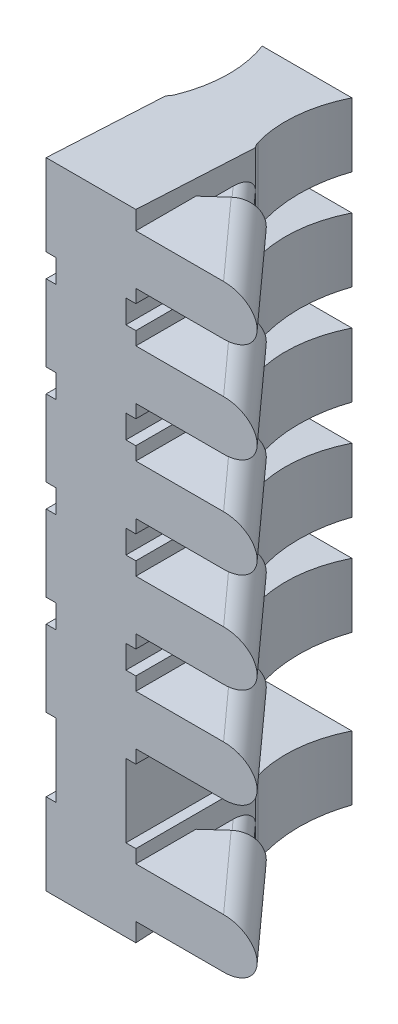
SolidWorks part; units mm, degrees
ref_plane "Front Plane" through (0, 0, 0) normal (0, 0, 1) x (1, 0, 0)
ref_plane "Top Plane" through (0, 0, 0) normal (0, 1, 0) x (1, 0, 0)
ref_plane "Right Plane" through (0, 0, 0) normal (1, 0, 0) x (0, 0, -1)
sketch "Sketch1" plane through (0, 0, 0) normal (0, 0, 1) x (1, 0, 0)
  line L0 (-7.5, 0) -> (0, 0) construction
  line L1 (-7.5, 15) -> (7.5, 15)
  line L2 (-7.5, 15) -> (-7.5, -15)
  line L3 (-7.5, -15) -> (7.5, -15)
  line L4 (7.5, 15) -> (7.5, -15)
  line L5 (0, 0) -> (0, 15) construction
  dimension "D1" = 15
  dimension "D2" = 30
sketch "Sketch2" plane through (0, 0, 0) normal (1, 0, 0) x (0, 0, -1)
  line L1 (0, 15) -> (7, 15)
  line L2 (0, 15) -> (0, -15)
  line L3 (0, -15) -> (7, -15)
  line L4 (7, 15) -> (7, -15)
  dimension "D1" = 7
extrude "Boss-Extrude1" add sketch "Sketch1" against normal up to vertex (7 mm away) up to point (0, 15, -7)
ref_plane "Plane1" through (1.35, 0, 0) normal (1, 0, 0) x (0, 0, -1)
sketch "Sketch7" plane through (1.35, 0, 0) normal (1, 0, 0) x (0, 0, -1)
  line L0 (3, 4.1005) -> (0, 4.1005) construction
  line L1 (0, 4.1005) -> (0, 6.3995) construction
  line L2 (3, 6.3995) -> (0, 6.3995) construction
  line L3 (3, 6.3995) -> (6.5, 6.2161) construction
  line L4 (6.5, 6.2161) -> (6.5, 4.2839) construction
  line L5 (6.5, 4.2839) -> (3, 4.1005) construction
  line L6 (3, 1.1005) -> (0, 1.1005) construction
  line L7 (0, 1.1005) -> (0, 3.3995) construction
  line L8 (3, 3.3995) -> (0, 3.3995) construction
  line L9 (6.5, 3.2161) -> (3, 3.3995) construction
  line L10 (6.5, 1.2839) -> (6.5, 3.2161) construction
  line L11 (3, 1.1005) -> (6.5, 1.2839) construction
  line L12 (3, -1.8995) -> (0, -1.8995) construction
  line L13 (0, -1.8995) -> (0, 0.3995) construction
  line L14 (3, 0.3995) -> (0, 0.3995) construction
  line L15 (3, 0.3995) -> (6.5, 0.2161) construction
  line L16 (6.5, 0.2161) -> (6.5, -1.7161) construction
  line L17 (6.5, -1.7161) -> (3, -1.8995) construction
  line L19 (3, -4.8995) -> (0, -4.8995) construction
  line L20 (0, -4.8995) -> (0, -2.6005) construction
  line L21 (3, -2.6005) -> (0, -2.6005) construction
  line L22 (6.5, -2.7839) -> (3, -2.6005) construction
  line L23 (6.5, -4.7161) -> (6.5, -2.7839) construction
  line L24 (3, -4.8995) -> (6.5, -4.7161) construction
  line L25 (3, -7.1005) -> (0, -7.1005) construction
  line L26 (0, -9.5567) -> (0, -7.1005) construction
  line L27 (6.5, -9.2161) -> (0, -9.5567) construction
  line L28 (6.5, -7.2839) -> (6.5, -9.2161) construction
  line L29 (3, -7.1005) -> (6.5, -7.2839) construction
  line L30 (3, 7.1005) -> (0, 7.1005) construction
  line L31 (0, 7.1005) -> (0, 9.5567) construction
  line L32 (6.5, 9.2161) -> (0, 9.5567) construction
  line L33 (6.5, 7.2839) -> (6.5, 9.2161) construction
  line L34 (3, 7.1005) -> (6.5, 7.2839) construction
  line L35 (3, 4.1005) -> (0, 4.1005)
  line L36 (0, 4.1005) -> (0, 6.3995)
  line L37 (3, 6.3995) -> (0, 6.3995)
  line L38 (3, 6.3995) -> (6.5, 6.2161)
  line L39 (6.5, 6.2161) -> (6.5, 4.2839)
  line L40 (6.5, 4.2839) -> (3, 4.1005)
  line L41 (3, 1.1005) -> (0, 1.1005)
  line L42 (0, 1.1005) -> (0, 3.3995)
  line L43 (3, 3.3995) -> (0, 3.3995)
  line L44 (6.5, 3.2161) -> (3, 3.3995)
  line L45 (6.5, 1.2839) -> (6.5, 3.2161)
  line L46 (3, 1.1005) -> (6.5, 1.2839)
  line L47 (3, -1.8995) -> (0, -1.8995)
  line L48 (0, -1.8995) -> (0, 0.3995)
  line L49 (3, 0.3995) -> (0, 0.3995)
  line L50 (3, 0.3995) -> (6.5, 0.2161)
  line L51 (6.5, 0.2161) -> (6.5, -1.7161)
  line L52 (6.5, -1.7161) -> (3, -1.8995)
  line L54 (3, -4.8995) -> (0, -4.8995)
  line L55 (0, -4.8995) -> (0, -2.6005)
  line L56 (3, -2.6005) -> (0, -2.6005)
  line L57 (6.5, -2.7839) -> (3, -2.6005)
  line L58 (6.5, -4.7161) -> (6.5, -2.7839)
  line L59 (3, -4.8995) -> (6.5, -4.7161)
  line L60 (3, -7.1005) -> (0, -7.1005)
  line L61 (0, -9.5567) -> (0, -7.1005)
  line L62 (6.5, -9.2161) -> (0, -9.5567)
  line L63 (6.5, -7.2839) -> (6.5, -9.2161)
  line L64 (3, -7.1005) -> (6.5, -7.2839)
  line L65 (3, 7.1005) -> (0, 7.1005)
  line L66 (0, 7.1005) -> (0, 9.5567)
  line L67 (6.5, 9.2161) -> (0, 9.5567)
  line L68 (6.5, 7.2839) -> (6.5, 9.2161)
  line L69 (3, 7.1005) -> (6.5, 7.2839)
sketch "Sketch8" plane through (1.35, 0, 0) normal (1, 0, 0) x (0, 0, -1)
  line L0 (6.5, -4.7161) -> (6.5, -2.7839) construction
  line L1 (6.5, -2.7839) -> (3, -2.6005) construction
  line L2 (3, -2.6005) -> (3, -1.8995) construction
  line L3 (6.5, -1.7161) -> (3, -1.8995) construction
  line L4 (6.5, 0.2161) -> (6.5, -1.7161) construction
  line L5 (3, 0.3995) -> (6.5, 0.2161) construction
  line L6 (3, 0.3995) -> (3, 1.1005) construction
  line L7 (3, 1.1005) -> (6.5, 1.2839) construction
  line L8 (6.5, 1.2839) -> (6.5, 3.2161) construction
  line L9 (6.5, 3.2161) -> (3, 3.3995) construction
  line L10 (3, 3.3995) -> (3, 4.1005) construction
  line L11 (6.5, 4.2839) -> (3, 4.1005) construction
  line L12 (6.5, 6.2161) -> (6.5, 4.2839) construction
  line L13 (3, 6.3995) -> (6.5, 6.2161) construction
  line L14 (3, 6.3995) -> (3, 7.1005) construction
  line L15 (3, 7.1005) -> (6.5, 7.2839) construction
  line L16 (6.5, 7.2839) -> (6.5, 9.2161) construction
  line L17 (6.5, 9.2161) -> (0, 9.5567) construction
  line L18 (0, 9.5567) -> (0, -9.5567) construction
  line L19 (6.5, -9.2161) -> (0, -9.5567) construction
  line L20 (6.5, -7.2839) -> (6.5, -9.2161) construction
  line L21 (3, -7.1005) -> (6.5, -7.2839) construction
  line L22 (3, -7.1005) -> (3, -4.8995) construction
  line L23 (3, -4.8995) -> (6.5, -4.7161) construction
  line L24 (6.5, -4.7161) -> (6.5, -2.7839)
  line L25 (6.5, -2.7839) -> (3, -2.6005)
  line L26 (3, -2.6005) -> (3, -1.8995)
  line L27 (6.5, -1.7161) -> (3, -1.8995)
  line L28 (6.5, 0.2161) -> (6.5, -1.7161)
  line L29 (3, 0.3995) -> (6.5, 0.2161)
  line L30 (3, 0.3995) -> (3, 1.1005)
  line L31 (3, 1.1005) -> (6.5, 1.2839)
  line L32 (6.5, 1.2839) -> (6.5, 3.2161)
  line L33 (6.5, 3.2161) -> (3, 3.3995)
  line L34 (3, 3.3995) -> (3, 4.1005)
  line L35 (6.5, 4.2839) -> (3, 4.1005)
  line L36 (6.5, 6.2161) -> (6.5, 4.2839)
  line L37 (3, 6.3995) -> (6.5, 6.2161)
  line L38 (3, 6.3995) -> (3, 7.1005)
  line L39 (3, 7.1005) -> (6.5, 7.2839)
  line L40 (6.5, 7.2839) -> (6.5, 9.2161)
  line L41 (6.5, 9.2161) -> (0, 9.5567)
  line L42 (0, 9.5567) -> (0, -9.5567)
  line L43 (6.5, -9.2161) -> (0, -9.5567)
  line L44 (6.5, -7.2839) -> (6.5, -9.2161)
  line L45 (3, -7.1005) -> (6.5, -7.2839)
  line L46 (3, -7.1005) -> (3, -4.8995)
  line L47 (3, -4.8995) -> (6.5, -4.7161)
sketch "Sketch9" plane through (0, 0, 0) normal (0, 0, 1) x (1, 0, 0)
  line L0 (-1.35, 9.5567) -> (-1.35, -9.5567) construction
  line L1 (1.35, -9.5567) -> (-1.35, -9.5567) construction
  line L2 (1.35, 9.5567) -> (1.35, -9.5567) construction
  line L3 (1.35, 9.5567) -> (-1.35, 9.5567) construction
  line L4 (-1.35, 9.5567) -> (-1.35, -9.5567) construction
  line L5 (1.35, -9.5567) -> (-1.35, -9.5567) construction
  line L6 (1.35, 9.5567) -> (1.35, -9.5567) construction
  line L7 (1.35, 9.5567) -> (-1.35, 9.5567) construction
  line L8 (0, -9.5567) -> (0, 9.5567) construction
  line L9 (-1.35, 0) -> (1.35, 0) construction
  line L10 (0.75, -9.1562) -> (-0.75, -9.1562) construction
  line L11 (-0.75, 9.1562) -> (-0.75, -9.1562) construction
  line L12 (0.75, 9.1562) -> (-0.75, 9.1562) construction
  line L13 (0.75, -9.1562) -> (-0.75, -9.1562)
  line L14 (-0.75, 9.1562) -> (-0.75, -9.1562)
  line L15 (0.75, 9.1562) -> (-0.75, 9.1562)
  line L16 (0.75, -9.1562) -> (0.75, 9.1562)
  line L17 (1.05, -9.5567) -> (1.05, 9.5567) construction
  line L18 (-1.05, -9.5567) -> (-1.05, 9.5567) construction
  line L19 (1.05, -9.5567) -> (1.05, 9.5567) construction
  line L20 (-1.05, -9.5567) -> (-1.05, 9.5567) construction
ref_plane "Plane2" through (0, -9.5567, 0) normal (0, 1, 0) x (1, 0, 0)
sketch "Sketch10" plane through (0, -9.5567, 0) normal (0, 1, 0) x (1, 0, 0)
  line L0 (1.35, 3.5995) -> (1.35, 6.5)
  line L1 (-1.35, 3.5995) -> (-1.35, 6.5)
  arc A0 (-1.2465, 3.7776) -> (-1.35, 6.5) centre (-4.95, 5) ccw construction
  arc A1 (-1.35, 3.5995) -> (-1.2465, 3.7776) centre (-1.7213, 3.9344) ccw construction
  arc A2 (1.2465, 3.7776) -> (1.35, 3.5995) centre (1.7213, 3.9344) ccw construction
  arc A3 (1.35, 6.5) -> (1.2465, 3.7776) centre (4.95, 5) ccw construction
  arc A4 (-1.2465, 3.7776) -> (-1.35, 6.5) centre (-4.95, 5) ccw
  arc A5 (-1.35, 3.5995) -> (-1.2465, 3.7776) centre (-1.7213, 3.9344) ccw
  arc A6 (1.2465, 3.7776) -> (1.35, 3.5995) centre (1.7213, 3.9344) ccw
  arc A7 (1.35, 6.5) -> (1.2465, 3.7776) centre (4.95, 5) ccw
ref_plane "Plane3" through (2.213, 9.1562, -4.3777) normal (0.6697, 0, 0.7426) x (0, -1, 0)
sketch "Sketch11" plane through (2.213, 9.1562, -4.3777) normal (0.6697, 0, 0.7426) x (0, -1, 0)
  line L0 (0.4562, -2.362) -> (0.4562, -1.612) construction
  line L1 (1.3562, -1.612) -> (1.3562, -2.362) construction
  line L2 (1.3562, -2.362) -> (0.4562, -2.362) construction
  line L3 (3.4562, -1.612) -> (3.4562, -2.362) construction
  line L4 (3.4562, -2.362) -> (4.3562, -2.362) construction
  line L5 (4.3562, -2.362) -> (4.3562, -1.612) construction
  line L6 (7.3562, -1.612) -> (7.3562, -2.362) construction
  line L7 (7.3562, -2.362) -> (6.4562, -2.362) construction
  line L8 (6.4562, -2.362) -> (6.4562, -1.612) construction
  line L9 (9.4562, -1.612) -> (9.4562, -2.362) construction
  line L10 (9.4562, -2.362) -> (10.3562, -2.362) construction
  line L11 (10.3562, -2.362) -> (10.3562, -1.612) construction
  line L12 (13.3562, -1.612) -> (13.3562, -2.362) construction
  line L13 (13.3562, -2.362) -> (12.4562, -2.362) construction
  line L14 (12.4562, -2.362) -> (12.4562, -1.612) construction
  line L15 (16.9562, -1.612) -> (16.9562, -2.362) construction
  line L16 (16.9562, -2.362) -> (17.8562, -2.362) construction
  line L17 (17.8562, -2.362) -> (17.8562, -1.612) construction
  line L18 (0.4562, -2.362) -> (0.4562, -1.612)
  line L19 (1.3562, -1.612) -> (1.3562, -2.362)
  line L20 (1.3562, -2.362) -> (0.4562, -2.362)
  line L21 (3.4562, -1.612) -> (3.4562, -2.362)
  line L22 (3.4562, -2.362) -> (4.3562, -2.362)
  line L23 (4.3562, -2.362) -> (4.3562, -1.612)
  line L24 (7.3562, -1.612) -> (7.3562, -2.362)
  line L25 (7.3562, -2.362) -> (6.4562, -2.362)
  line L26 (6.4562, -2.362) -> (6.4562, -1.612)
  line L27 (9.4562, -1.612) -> (9.4562, -2.362)
  line L28 (9.4562, -2.362) -> (10.3562, -2.362)
  line L29 (10.3562, -2.362) -> (10.3562, -1.612)
  line L30 (13.3562, -1.612) -> (13.3562, -2.362)
  line L31 (13.3562, -2.362) -> (12.4562, -2.362)
  line L32 (12.4562, -2.362) -> (12.4562, -1.612)
  line L33 (16.9562, -1.612) -> (16.9562, -2.362)
  line L34 (16.9562, -2.362) -> (17.8562, -2.362)
  line L35 (17.8562, -2.362) -> (17.8562, -1.612)
  arc A0 (1.3562, -1.612) -> (0.4562, -1.612) centre (0.9062, -1.612) ccw construction
  arc A1 (4.3562, -1.612) -> (3.4562, -1.612) centre (3.9062, -1.612) ccw construction
  arc A2 (7.3562, -1.612) -> (6.4562, -1.612) centre (6.9062, -1.612) ccw construction
  arc A3 (10.3562, -1.612) -> (9.4562, -1.612) centre (9.9062, -1.612) ccw construction
  arc A4 (13.3562, -1.612) -> (12.4562, -1.612) centre (12.9062, -1.612) ccw construction
  arc A5 (17.8562, -1.612) -> (16.9562, -1.612) centre (17.4062, -1.612) ccw construction
  arc A6 (1.3562, -1.612) -> (0.4562, -1.612) centre (0.9062, -1.612) ccw
  arc A7 (4.3562, -1.612) -> (3.4562, -1.612) centre (3.9062, -1.612) ccw
  arc A8 (7.3562, -1.612) -> (6.4562, -1.612) centre (6.9062, -1.612) ccw
  arc A9 (10.3562, -1.612) -> (9.4562, -1.612) centre (9.9062, -1.612) ccw
  arc A10 (13.3562, -1.612) -> (12.4562, -1.612) centre (12.9062, -1.612) ccw
  arc A11 (17.8562, -1.612) -> (16.9562, -1.612) centre (17.4062, -1.612) ccw
ref_plane "Plane4" through (3.1041, 9.1562, -3.3895) normal (0.6697, 0, 0.7426) x (0, -1, 0)
sketch "Sketch12" plane through (3.1041, 9.1562, -3.3895) normal (0.6697, 0, 0.7426) x (0, -1, 0)
  line L0 (0.1562, -1.612) -> (0.1562, -5.0612) construction
  line L1 (0.1562, -5.0612) -> (1.6562, -5.0612) construction
  line L2 (1.6562, -1.612) -> (1.6562, -5.0612) construction
  line L3 (3.1562, -1.612) -> (3.1562, -5.0612) construction
  line L4 (4.6562, -5.0612) -> (3.1562, -5.0612) construction
  line L5 (4.6562, -1.612) -> (4.6562, -5.0612) construction
  line L6 (6.1562, -1.612) -> (6.1562, -5.0612) construction
  line L7 (6.1562, -5.0612) -> (7.6562, -5.0612) construction
  line L8 (7.6562, -1.612) -> (7.6562, -5.0612) construction
  line L9 (9.1562, -1.612) -> (9.1562, -5.0612) construction
  line L10 (10.6562, -5.0612) -> (9.1562, -5.0612) construction
  line L11 (10.6562, -1.612) -> (10.6562, -5.0612) construction
  line L12 (12.1562, -1.612) -> (12.1562, -5.0612) construction
  line L13 (12.1562, -5.0612) -> (13.6562, -5.0612) construction
  line L14 (13.6562, -1.612) -> (13.6562, -5.0612) construction
  line L15 (16.6562, -1.612) -> (16.6562, -5.0612) construction
  line L16 (18.1562, -5.0612) -> (16.6562, -5.0612) construction
  line L17 (18.1562, -1.612) -> (18.1562, -5.0612) construction
  line L18 (0.1562, -1.612) -> (0.1562, -5.0612)
  line L19 (0.1562, -5.0612) -> (1.6562, -5.0612)
  line L20 (1.6562, -1.612) -> (1.6562, -5.0612)
  line L21 (3.1562, -1.612) -> (3.1562, -5.0612)
  line L22 (4.6562, -5.0612) -> (3.1562, -5.0612)
  line L23 (4.6562, -1.612) -> (4.6562, -5.0612)
  line L24 (6.1562, -1.612) -> (6.1562, -5.0612)
  line L25 (6.1562, -5.0612) -> (7.6562, -5.0612)
  line L26 (7.6562, -1.612) -> (7.6562, -5.0612)
  line L27 (9.1562, -1.612) -> (9.1562, -5.0612)
  line L28 (10.6562, -5.0612) -> (9.1562, -5.0612)
  line L29 (10.6562, -1.612) -> (10.6562, -5.0612)
  line L30 (12.1562, -1.612) -> (12.1562, -5.0612)
  line L31 (12.1562, -5.0612) -> (13.6562, -5.0612)
  line L32 (13.6562, -1.612) -> (13.6562, -5.0612)
  line L33 (16.6562, -1.612) -> (16.6562, -5.0612)
  line L34 (18.1562, -5.0612) -> (16.6562, -5.0612)
  line L35 (18.1562, -1.612) -> (18.1562, -5.0612)
  arc A0 (1.6562, -1.612) -> (0.1562, -1.612) centre (0.9062, -1.612) ccw construction
  arc A1 (4.6562, -1.612) -> (3.1562, -1.612) centre (3.9062, -1.612) ccw construction
  arc A2 (7.6562, -1.612) -> (6.1562, -1.612) centre (6.9062, -1.612) ccw construction
  arc A3 (10.6562, -1.612) -> (9.1562, -1.612) centre (9.9062, -1.612) ccw construction
  arc A4 (13.6562, -1.612) -> (12.1562, -1.612) centre (12.9062, -1.612) ccw construction
  arc A5 (18.1562, -1.612) -> (16.6562, -1.612) centre (17.4062, -1.612) ccw construction
  arc A6 (1.6562, -1.612) -> (0.1562, -1.612) centre (0.9062, -1.612) ccw
  arc A7 (4.6562, -1.612) -> (3.1562, -1.612) centre (3.9062, -1.612) ccw
  arc A8 (7.6562, -1.612) -> (6.1562, -1.612) centre (6.9062, -1.612) ccw
  arc A9 (10.6562, -1.612) -> (9.1562, -1.612) centre (9.9062, -1.612) ccw
  arc A10 (13.6562, -1.612) -> (12.1562, -1.612) centre (12.9062, -1.612) ccw
  arc A11 (18.1562, -1.612) -> (16.6562, -1.612) centre (17.4062, -1.612) ccw
extrude "Cut-Extrude1" cut sketch "Sketch8" against normal up to vertex (2.4 mm away) from vertex up to point (-1.05, -9.5567, 0) starting at point (1.05, -9.5567, 0)
extrude "Cut-Extrude4" cut sketch "Sketch7" against normal up to vertex (2.7 mm away) up to point (-1.35, -9.5567, 0)
extrude "Boss-Extrude2" add sketch "Sketch10" along normal up to vertex (19.1135 mm away) up to point (-1.35, 9.5567, 0)
extrude "Cut-Extrude2" cut sketch "Sketch12" along normal through all
extrude "Cut-Extrude3" cut sketch "Sketch11" along normal through all
mirror "Mirror1" about plane through (0, 0, 0) normal (1, 0, 0) of "Cut-Extrude2", "Cut-Extrude3"
sketch "Sketch13" plane through (0, 0, 0) normal (0, 0, 1) x (1, 0, 0)
  line L0 (0, 0) -> (-5, 0) construction
  line L1 (-5, -10) -> (5, -10)
  line L2 (-5, -10) -> (-5, 10)
  line L3 (-5, 10) -> (5, 10)
  line L4 (5, -10) -> (5, 10)
  line L5 (0, 0) -> (5, 0) construction
  line L6 (0, 0) -> (0, 10) construction
  line L7 (0, 0) -> (0, -10) construction
  dimension "D1" = 20
  dimension "D2" = 10
extrude "Boss-Extrude3" add sketch "Sketch13" against normal blind 7 separate body
combine bodies "Combine1" operation type subtract main body 114 bodies to subtract 112
sketch "Sketch14" plane through (0, 0, 0) normal (0, 0, 1) x (1, 0, 0)
  line L1 (-1.35, -9.5567) -> (-5, -9.5567)
  line L2 (-1.35, -9.5567) -> (-1.35, 9.5567)
  line L3 (-1.35, 9.5567) -> (-5, 9.5567)
  line L4 (-5, -9.5567) -> (-5, 9.5567)
  ellipse E0 centre (-3.9901, 8.25) end of major axis (-2.9802, 8.25) minor radius 0.75 (-3.9901, 9) -> (-3.9901, 7.5) ccw construction
extrude "Cut-Extrude5" cut sketch "Sketch14" against normal through all
